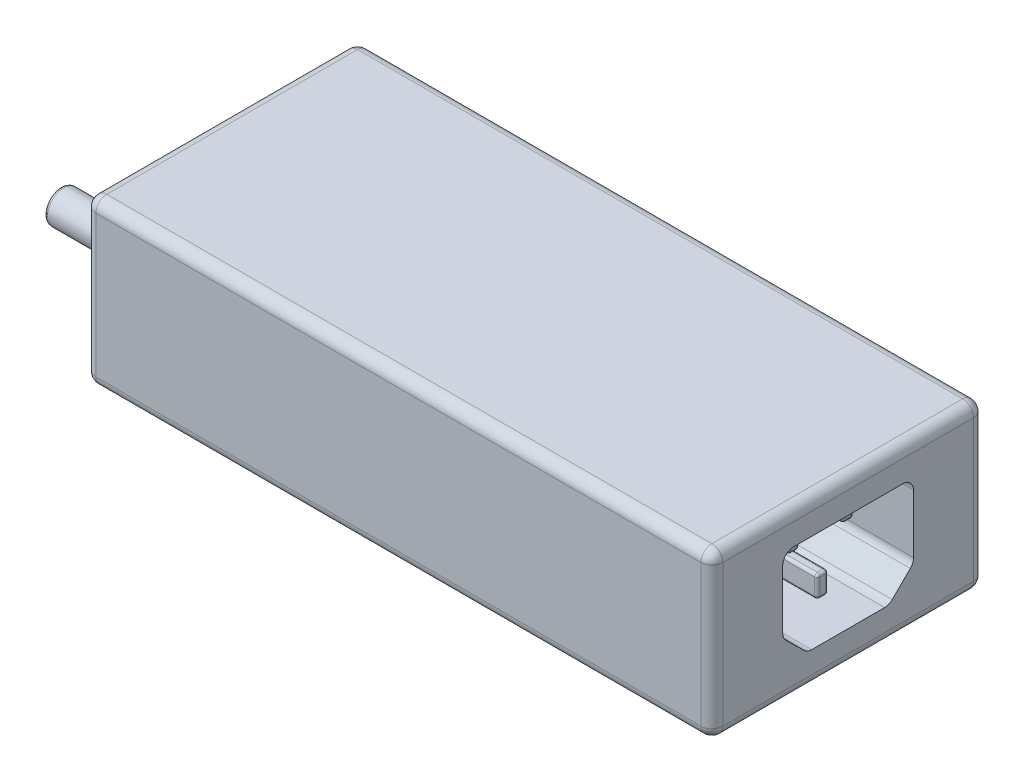
SolidWorks part; units mm, degrees
ref_plane "Front Plane" through (0, 0, 0) normal (0, 0, 1) x (1, 0, 0)
ref_plane "Top Plane" through (0, 0, 0) normal (0, 1, 0) x (1, 0, 0)
ref_plane "Right Plane" through (0, 0, 0) normal (1, 0, 0) x (0, 0, -1)
sketch "Sketch1" plane through (0, 0, 0) normal (0, 1, 0) x (1, 0, 0)
  line L1 (-57.5, 25) -> (57.5, 25)
  line L2 (-57.5, 25) -> (-57.5, -25)
  line L3 (-57.5, -25) -> (57.5, -25)
  line L4 (57.5, 25) -> (57.5, -25)
  line L5 (-57.5, 25) -> (57.5, -25) construction
  line L6 (-57.5, -25) -> (57.5, 25) construction
  point P0 (0, 0)
  dimension "D1" = 50
  dimension "D2" = 115
extrude "Boss-Extrude1" add sketch "Sketch1" along normal blind 30 contours L1 L4 L3 L2
fillet "Fillet1" radius 2 12 edges at (-57.5, 0, 0) (-57.5, 15, -25) (-57.5, 30, 0) (0, 0, -25) (0, 30, -25) (57.5, 15, -25) (57.5, 30, 0) (57.5, 0, 0) (57.5, 15, 25) (-57.5, 15, 25) (0, 0, 25) (0, 30, 25)
sketch "Sketch2" plane through (57.5, 0, 0) normal (1, 0, 0) x (0, 0, -1)
  line L0 (-10, 24) -> (10, 24)
  line L1 (12, 22) -> (12, 11.2727)
  line L2 (11.404, 9.8484) -> (8.084, 6.5757)
  line L3 (6.68, 6) -> (-6.68, 6)
  line L4 (-8.084, 6.5757) -> (-11.404, 9.8484)
  line L5 (-12, 11.2727) -> (-12, 22)
  line L6 (0, 0) -> (0, 31.7966) construction
  line L9 (-23, 30) -> (23, 30) construction
  arc A0 (-12, 22) -> (-10, 24) centre (-10, 22) cw
  arc A1 (12, 22) -> (10, 24) centre (10, 22) ccw
  arc A2 (6.68, 6) -> (8.084, 6.5757) centre (6.68, 8) ccw
  arc A3 (-6.68, 6) -> (-8.084, 6.5757) centre (-6.68, 8) cw
  arc A4 (-11.404, 9.8484) -> (-12, 11.2727) centre (-10, 11.2727) cw
  arc A5 (11.404, 9.8484) -> (12, 11.2727) centre (10, 11.2727) ccw
  point P8 (-12, 24)
  point P11 (12, 24)
  point P14 (7.5, 6)
  point P17 (-7.5, 6)
  point P20 (-12, 10.4359)
  dimension "D4" = 2
  dimension "D5" = 2
  dimension "D1" = 24
  dimension "D2" = 6
  dimension "D3" = 15
  dimension "D6" = 12
  dimension "D7" = 18
extrude "Cut-Extrude1" cut sketch "Sketch2" against normal blind 20
sketch "Sketch3" plane through (37.5, 0, 0) normal (1, 0, 0) x (0, 0, -1)
  line L0 (-12, 22) -> (-12, 11.2727) construction
  line L1 (-6, 22.0924) -> (-4, 22.0924)
  line L2 (-6, 22.0924) -> (-6, 18.0924)
  line L3 (-6, 18.0924) -> (-4, 18.0924)
  line L4 (-4, 22.0924) -> (-4, 18.0924)
  line L5 (-6, 22.0924) -> (-4, 18.0924) construction
  line L6 (-6, 18.0924) -> (-4, 22.0924) construction
  line L7 (-0.6522, 12.2657) -> (1.3478, 12.2657)
  line L8 (-0.6522, 12.2657) -> (-0.6522, 8.2657)
  line L9 (-0.6522, 8.2657) -> (1.3478, 8.2657)
  line L10 (1.3478, 12.2657) -> (1.3478, 8.2657)
  line L11 (-0.6522, 12.2657) -> (1.3478, 8.2657) construction
  line L12 (-0.6522, 8.2657) -> (1.3478, 12.2657) construction
  line L13 (4, 22.0924) -> (6, 22.0924)
  line L14 (4, 22.0924) -> (4, 18.0924)
  line L15 (4, 18.0924) -> (6, 18.0924)
  line L16 (6, 22.0924) -> (6, 18.0924)
  line L17 (4, 22.0924) -> (6, 18.0924) construction
  line L18 (4, 18.0924) -> (6, 22.0924) construction
  line L19 (-5, 20.0924) -> (5, 20.0924) construction
  point P0 (-5, 20.0924)
  point P5 (0.3478, 10.2657)
  point P13 (5, 20.0924)
  dimension "D1" = 7
  dimension "D2" = 2
  dimension "D3" = 2
  dimension "D4" = 4
  dimension "D5" = 4
  dimension "D6" = 10
  dimension "D7" = 2
extrude "Boss-Extrude2" add sketch "Sketch3" along normal blind 15
fillet "Fillet2" radius 0.5 36 edges at (37.5, 10.2657, 0.6522) (45, 8.2657, 0.6522) (45, 12.2657, 0.6522) (45, 8.2657, -1.3478) (45, 12.2657, -1.3478) (37.5, 10.2657, -1.3478) (52.5, 10.2657, 0.6522) (52.5, 10.2657, -1.3478) (37.5, 20.0924, -6) (45, 22.0924, -6) (45, 22.0924, -4) (37.5, 20.0924, -4) (52.5, 20.0924, -4) (52.5, 20.0924, -6) (45, 18.0924, -4) (45, 18.0924, -6) (45, 18.0924, 6) (37.5, 20.0924, 6) (52.5, 20.0924, 6) (45, 18.0924, 4) (52.5, 20.0924, 4) (37.5, 20.0924, 4) (45, 22.0924, 4) (45, 22.0924, 6) (37.5, 8.2657, -0.3478) (37.5, 12.2657, -0.3478) (52.5, 8.2657, -0.3478) (52.5, 12.2657, -0.3478) (37.5, 22.0924, -5) (52.5, 22.0924, -5) (52.5, 18.0924, -5) (37.5, 18.0924, -5) (37.5, 18.0924, 5) (52.5, 18.0924, 5) (52.5, 22.0924, 5) (37.5, 22.0924, 5)
sketch "Sketch6" plane through (-57.5, 0, 0) normal (-1, 0, 0) x (0, 0, 1)
  circle A0 centre (14.3991, 15.4766) radius 3
extrude "Boss-Extrude3" add sketch "Sketch6" along normal blind 15
fillet "Fillet4" radius 0.5 1 edges at (-72.5, 15.4766, 17.3991)
